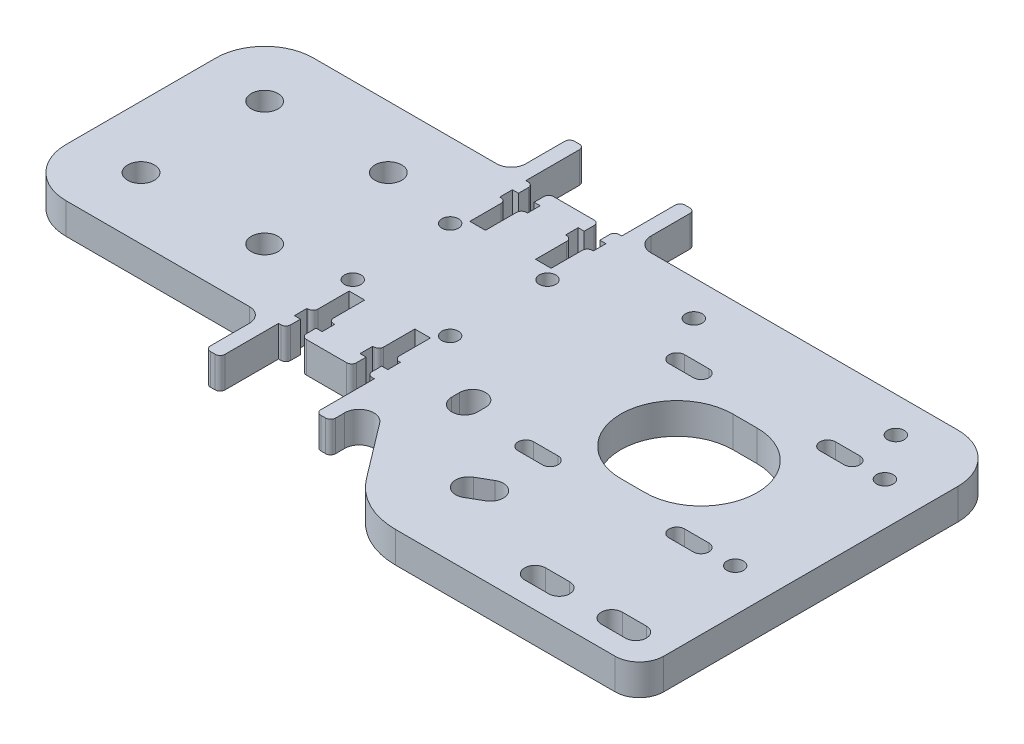
SolidWorks part; units mm, degrees
ref_plane "Front" through (0, 0, 0) normal (0, 0, 1) x (1, 0, 0)
ref_plane "Top" through (0, 0, 0) normal (0, 1, 0) x (1, 0, 0)
ref_plane "Right" through (0, 0, 0) normal (1, 0, 0) x (0, 0, -1)
sketch "Sketch1" plane through (0, 0, 0) normal (0, 1, 0) x (1, 0, 0)
  line L0 (0, 0) -> (114.3212, 0) construction
  line L1 (38.1, -25.4) -> (-38.1, -25.4)
  line L2 (38.1, -25.4) -> (38.1, 25.4) construction
  line L3 (38.1, 25.4) -> (-38.1, 25.4)
  line L4 (-38.1, -25.4) -> (-38.1, 25.4)
  line L5 (38.1, -25.4) -> (-38.1, 25.4) construction
  line L6 (38.1, 25.4) -> (-38.1, -25.4) construction
  line L7 (25.4, 25.4) -> (25.4, -25.4) construction
  line L8 (-25.4, 25.4) -> (-25.4, -25.4) construction
  line L9 (0, -25.4) -> (0, 25.4) construction
  line L10 (0, 0) -> (-38.1, 0) construction
  line L11 (-25.4, 0) -> (-25.4, 25.4) construction
  line L12 (-25.4, 12.7) -> (0, 12.7) construction
  line L13 (25.4, -41.4) -> (114.3212, -41.4) construction
  line L14 (99.3212, -27.36) -> (57.3212, -27.36) construction
  line L15 (99.3212, -27.36) -> (99.3212, 14.64) construction
  line L16 (99.3212, 14.64) -> (57.3212, 14.64) construction
  line L17 (57.3212, -27.36) -> (57.3212, 14.64) construction
  line L18 (99.3212, -27.36) -> (57.3212, 14.64) construction
  line L19 (99.3212, 14.64) -> (57.3212, -27.36) construction
  line L20 (93.8212, -21.86) -> (62.8212, -21.86) construction
  line L21 (93.8212, -21.86) -> (93.8212, 9.14) construction
  line L22 (93.8212, 9.14) -> (62.8212, 9.14) construction
  line L23 (62.8212, -21.86) -> (62.8212, 9.14) construction
  line L24 (93.8212, -21.86) -> (62.8212, 9.14) construction
  line L25 (93.8212, 9.14) -> (62.8212, -21.86) construction
  line L26 (114.3212, -41.4) -> (114.3212, 0) construction
  line L27 (49.1, -12.72) -> (78.3212, -12.72) construction
  line L28 (47.8664, -25.3192) -> (65.4755, -28.8008) construction
  line L29 (38.1, -25.4) -> (52.2919, -44.1062)
  line L30 (78.3212, 0) -> (0, 0) construction
  line L31 (35.4, 10) -> (15.4, 10) construction
  line L32 (64.2419, -50.04) -> (114.3212, -50.04)
  line L33 (114.3212, -50.04) -> (114.3212, 25.4)
  line L34 (114.3212, 25.4) -> (38.1, 25.4)
  line L35 (49.1, -19.08) -> (49.1, -20.72) construction
  line L36 (64.2419, -35.04) -> (67.0783, -33.4) construction
  line L37 (64.2419, -35.04) -> (64.2419, -50.04) construction
  circle A0 centre (-25.4, 12.7) radius 2.5 construction
  circle A1 centre (0, 12.7) radius 2.5 construction
  circle A2 centre (-25.4, -12.7) radius 2.5 construction
  circle A3 centre (0, -12.7) radius 2.5 construction
  circle A4 centre (78.3212, -6.36) radius 6.36 construction
  circle A5 centre (78.3212, -6.36) radius 11 construction
  circle A6 centre (62.8212, 9.14) radius 1.5 construction
  circle A7 centre (93.8212, 9.14) radius 1.5 construction
  circle A8 centre (93.8212, -21.86) radius 1.5 construction
  circle A9 centre (62.8212, -21.86) radius 1.5 construction
  circle A10 centre (64.2419, -35.04) radius 6.36 construction
  circle A11 centre (64.2419, -35.04) radius 11 construction
  circle A12 centre (49.1, -19.08) radius 6.36 construction
  circle A13 centre (49.1, -19.08) radius 11 construction
  circle A14 centre (62.8212, -21.86) radius 3 construction
  circle A15 centre (35.4, 10) radius 1.5 construction
  circle A16 centre (15.4, 10) radius 1.5 construction
  circle A17 centre (35.4, -10) radius 1.5 construction
  circle A18 centre (15.4, -10) radius 1.5 construction
  circle A19 centre (49.1, -19.08) radius 2.5 construction
  circle A20 centre (64.2419, -35.04) radius 2.5 construction
  circle A21 centre (78.3212, -6.36) radius 11 construction
  arc A22 (52.2919, -44.1062) -> (64.2419, -50.04) centre (64.2419, -35.04) ccw
  circle A23 centre (49.1, -20.72) radius 8 construction
  circle A24 centre (49.1, -20.72) radius 11 construction
  circle A25 centre (67.0783, -33.4) radius 8 construction
  circle A26 centre (67.0783, -33.4) radius 11 construction
  point P0 (0, 0)
  point P54 (25.4, 10)
  dimension "D6" = 5
  dimension "D7" = 12.72
  dimension "D9" = 22
  dimension "D11" = 3
  dimension "D12" = 16
  dimension "D13" = 6
  dimension "D16" = 3
  dimension "D17" = 5
  dimension "D18" = 22
  dimension "D20" = 16
  dimension "D21" = 4
  dimension "D1" = 50.8
  dimension "D2" = 76.2
  dimension "D3" = 12.7
  dimension "D4" = 12.7
  dimension "D5" = 25.4
  dimension "D8" = 42
  dimension "D10" = 31
  dimension "D14" = 20
  dimension "D15" = 10
  dimension "D19" = 15
extrude "Boss-Extrude1" add sketch "Sketch1" along normal blind 6.35
hole_wizard "M5 Clearance Hole1" positions "Sketch3" profile "Sketch2" hole size "M5" standard "ISO" end condition through all
sketch "Sketch3" plane through (0, 6.35, 0) normal (0, 1, 0) x (1, 0, 0)
  point P0 (-25.4, 12.7)
  point P3 (0, 12.7)
  point P6 (0, -12.7)
  point P9 (-25.4, -12.7)
sketch "Sketch2" plane through (-25.4, 6.35, -12.7) normal (1, 0, 0) x (0, 0, 1)
  line L0 (0, 0) -> (0, 6.35)
  line L1 (0, 6.35) -> (2.75, 6.35)
  line L2 (2.75, 6.35) -> (2.75, 0)
  line L5 (2.75, 0) -> (0, 0)
  line L11 (0, -6.35) -> (0, 107.95) construction
  dimension "Thru Hole Dia." = 5.5
  dimension "Thru Hole Depth" = 6.35
hole_wizard "M3 Clearance Hole1" positions "Sketch5" profile "Sketch4" hole size "M3" standard "ISO" end condition through all
sketch "Sketch5" plane through (0, 6.35, 0) normal (0, 1, 0) x (1, 0, 0)
  point P0 (15.4, 10)
  point P3 (35.4, 10)
  point P6 (35.4, -10)
  point P9 (15.4, -10)
sketch "Sketch4" plane through (15.4, 6.35, -10) normal (1, 0, 0) x (0, 0, 1)
  line L0 (0, 0) -> (0, 6.35)
  line L1 (0, 6.35) -> (1.7, 6.35)
  line L2 (1.7, 6.35) -> (1.7, 0)
  line L5 (1.7, 0) -> (0, 0)
  line L11 (0, -6.35) -> (0, 107.95) construction
  dimension "Thru Hole Dia." = 3.4
  dimension "Thru Hole Depth" = 6.35
sketch "Sketch6" plane through (0, 6.35, 0) normal (0, 1, 0) x (1, 0, 0)
  line L0 (62.8212, 9.14) -> (67.8212, 9.14) construction
  line L1 (93.8212, 9.14) -> (62.8212, 9.14) construction
  line L2 (62.8212, -21.86) -> (67.8212, -21.86) construction
  line L3 (93.8212, -21.86) -> (62.8212, -21.86) construction
  line L4 (93.8212, -21.86) -> (98.8212, -21.86) construction
  line L5 (93.8212, 9.14) -> (98.8212, 9.14) construction
  line L6 (62.8212, 7.54) -> (67.8212, 7.54)
  line L7 (62.8212, -23.46) -> (67.8212, -23.46)
  line L8 (93.8212, -23.46) -> (98.8212, -23.46)
  line L9 (93.8212, 7.54) -> (98.8212, 7.54)
  line L10 (62.8212, 10.74) -> (67.8212, 10.74)
  line L11 (62.8212, -20.26) -> (67.8212, -20.26)
  line L12 (93.8212, -20.26) -> (98.8212, -20.26)
  line L13 (93.8212, 10.74) -> (98.8212, 10.74)
  line L14 (78.3212, -6.36) -> (83.3212, -6.36) construction
  line L15 (99.3212, 14.64) -> (57.3212, -27.36) construction
  line L16 (78.3212, -17.86) -> (83.3212, -17.86)
  line L17 (78.3212, 5.14) -> (83.3212, 5.14)
  arc A0 (62.8212, 7.54) -> (62.8212, 10.74) centre (62.8212, 9.14) cw
  arc A1 (67.8212, 7.54) -> (67.8212, 10.74) centre (67.8212, 9.14) ccw
  arc A2 (62.8212, -23.46) -> (62.8212, -20.26) centre (62.8212, -21.86) cw
  arc A3 (67.8212, -23.46) -> (67.8212, -20.26) centre (67.8212, -21.86) ccw
  arc A4 (93.8212, -23.46) -> (93.8212, -20.26) centre (93.8212, -21.86) cw
  arc A5 (98.8212, -23.46) -> (98.8212, -20.26) centre (98.8212, -21.86) ccw
  arc A6 (93.8212, 7.54) -> (93.8212, 10.74) centre (93.8212, 9.14) cw
  arc A7 (98.8212, 7.54) -> (98.8212, 10.74) centre (98.8212, 9.14) ccw
  arc A8 (78.3212, -17.86) -> (78.3212, 5.14) centre (78.3212, -6.36) cw
  arc A9 (83.3212, -17.86) -> (83.3212, 5.14) centre (83.3212, -6.36) ccw
  dimension "D1" = 5
  dimension "D2" = 1.6
  dimension "D3" = 1.6
  dimension "D4" = 11.5
  dimension "D5" = 11.5
extrude "Cut-Extrude1" cut sketch "Sketch6" against normal through all
sketch "Sketch7" plane through (0, 6.35, 0) normal (0, 1, 0) x (1, 0, 0)
  line L0 (49.1, -19.08) -> (49.1, -20.72) construction
  line L1 (67.0783, -33.4) -> (64.2419, -35.04) construction
  line L2 (65.7518, -31.1059) -> (62.9155, -32.7459)
  line L3 (46.45, -19.08) -> (46.45, -20.72)
  line L4 (68.4047, -35.6941) -> (65.5684, -37.3341)
  line L5 (51.75, -19.08) -> (51.75, -20.72)
  arc A0 (65.7518, -31.1059) -> (68.4047, -35.6941) centre (67.0783, -33.4) cw
  arc A1 (62.9155, -32.7459) -> (65.5684, -37.3341) centre (64.2419, -35.04) ccw
  arc A2 (46.45, -19.08) -> (51.75, -19.08) centre (49.1, -19.08) cw
  arc A3 (46.45, -20.72) -> (51.75, -20.72) centre (49.1, -20.72) ccw
  dimension "D1" = 2.65
  dimension "D2" = 2.65
extrude "Cut-Extrude2" cut sketch "Sketch7" against normal through all
fillet "Fillet1" radius 10 3 edges at (114.3212, 3.175, -25.4) (-38.1, 3.175, -25.4) (-38.1, 3.175, 25.4)
sketch "Sketch8" plane through (0, 6.35, 0) normal (0, 1, 0) x (1, 0, 0)
  line L0 (114.3212, -43.61) -> (79.3212, -43.61) construction
  line L1 (114.3212, -50.04) -> (114.3212, 15.4) construction
  line L2 (89.0712, -43.61) -> (104.5712, -43.61) construction
  line L3 (96.8212, -43.61) -> (96.8212, -25.11) construction
  line L4 (114.3212, -25.11) -> (79.3212, -25.11) construction
  line L5 (79.3212, -25.11) -> (79.3212, -57.11) construction
  line L6 (79.3212, -57.11) -> (114.3212, -57.11) construction
  line L7 (114.3212, -57.11) -> (114.3212, -25.11) construction
  line L8 (107.1712, -41.46) -> (102.2212, -41.46)
  line L9 (86.4712, -43.61) -> (91.4212, -43.61) construction
  line L10 (86.4712, -45.76) -> (91.4212, -45.76)
  line L11 (86.4712, -41.46) -> (91.4212, -41.46)
  line L12 (84.3212, -43.61) -> (84.3212, -50.04) construction
  line L13 (64.2419, -50.04) -> (114.3212, -50.04) construction
  line L14 (93.5712, -43.61) -> (93.5712, -50.04) construction
  line L15 (107.1712, -45.76) -> (102.2212, -45.76)
  circle A0 centre (104.5712, -43.61) radius 2 construction
  circle A1 centre (89.0712, -43.61) radius 2 construction
  arc A2 (86.4712, -45.76) -> (86.4712, -41.46) centre (86.4712, -43.61) cw
  arc A3 (91.4212, -45.76) -> (91.4212, -41.46) centre (91.4212, -43.61) ccw
  circle A4 centre (93.8212, -21.86) radius 3.25 construction
  circle A5 centre (67.0783, -33.4) radius 11 construction
  arc A6 (107.1712, -41.46) -> (107.1712, -45.76) centre (107.1712, -43.61) cw
  arc A7 (102.2212, -41.46) -> (102.2212, -45.76) centre (102.2212, -43.61) ccw
  point P13 (96.8212, -25.11)
  dimension "D3" = 4
  dimension "D11" = 6.5
  dimension "D12" = 22
  dimension "D2" = 15.5
  dimension "D4" = 18.5
  dimension "D5" = 32
  dimension "D8" = 25
  dimension "D9" = 6.5
  dimension "D10" = 35
  dimension "D6" = 2.15
  dimension "D7" = 2.15
extrude "Cut-Extrude3" cut sketch "Sketch8" against normal through all
sketch "Sketch10" plane through (0, 6.35, 0) normal (0, 1, 0) x (1, 0, 0)
  line L0 (114.3212, -25.11) -> (79.3212, -25.11) construction
  line L1 (57.3212, 14.64) -> (57.3212, 18.14) construction
  line L2 (57.3212, 18.14) -> (98.8212, 18.14) construction
  line L3 (98.8212, 18.14) -> (98.8212, 9.14) construction
  line L4 (98.8212, 9.14) -> (105.5666, 9.14) construction
  line L5 (105.5666, 9.14) -> (105.5666, -21.61) construction
  line L7 (99.3212, 14.64) -> (57.3212, 14.64) construction
  circle A0 centre (105.5666, -21.61) radius 3.5
  circle A1 centre (98.8212, -21.86) radius 3.25 construction
  circle A2 centre (98.8212, 9.14) radius 3.25 construction
  circle A3 centre (105.5666, 9.14) radius 3.5
  circle A4 centre (98.8212, 18.14) radius 3.5
  circle A5 centre (57.3212, 18.14) radius 3.5
  dimension "D1" = 6.5
  dimension "D2" = 7
hole_wizard "M3 Clearance Hole2" positions "Sketch12" profile "Sketch11" hole size "M3" standard "ISO" end condition through all
sketch "Sketch12" plane through (0, 6.35, 0) normal (0, 1, 0) x (1, 0, 0)
  point P0 (57.3212, 18.14)
  point P3 (98.8212, 18.14)
  point P6 (105.5666, 9.14)
  point P9 (105.5666, -21.61)
sketch "Sketch11" plane through (57.3212, 6.35, -18.14) normal (1, 0, 0) x (0, 0, 1)
  line L0 (0, 0) -> (0, 6.35)
  line L1 (0, 6.35) -> (1.7, 6.35)
  line L2 (1.7, 6.35) -> (1.7, 0)
  line L5 (1.7, 0) -> (0, 0)
  line L11 (0, -6.35) -> (0, 107.95) construction
  dimension "Thru Hole Dia." = 3.4
  dimension "Thru Hole Depth" = 6.35
fillet "Fillet3" radius 5 1 edges at (114.3212, 3.175, 50.04)
sketch "Sketch13" plane through (0, 6.35, 0) normal (0, 1, 0) x (1, 0, 0)
  line L0 (25.4, 25.4) -> (25.4, -25.4) construction
  line L1 (38.1, 25.4) -> (-38.1, 25.4) construction
  line L2 (35.25, 25.4) -> (38.25, 25.4)
  line L3 (35.25, 25.4) -> (35.25, 37.4)
  line L4 (35.25, 37.4) -> (38.25, 37.4)
  line L5 (38.25, 25.4) -> (38.25, 37.4)
  line L6 (12.55, 25.4) -> (12.55, 37.4)
  line L7 (15.55, 37.4) -> (12.55, 37.4)
  line L8 (15.55, 25.4) -> (15.55, 37.4)
  line L9 (15.55, 25.4) -> (12.55, 25.4)
  line L10 (0, 0) -> (38.1, 0) construction
  line L11 (38.1, -25.4) -> (38.1, 25.4) construction
  line L12 (15.55, -25.4) -> (12.55, -25.4)
  line L13 (15.55, -25.4) -> (15.55, -37.4)
  line L14 (15.55, -37.4) -> (12.55, -37.4)
  line L15 (12.55, -25.4) -> (12.55, -37.4)
  line L16 (38.25, -25.4) -> (38.25, -37.4)
  line L17 (35.25, -37.4) -> (38.25, -37.4)
  line L18 (35.25, -25.4) -> (35.25, -37.4)
  line L19 (35.25, -25.4) -> (38.25, -25.4)
  dimension "D1" = 12
  dimension "D2" = 3
  dimension "D3" = 19.7
extrude "Boss-Extrude2" add sketch "Sketch13" against normal up to surface (6.35 mm away) up to face at (57.3212, 0, -16.44)
fillet "Fillet4" radius 3 4 edges at (38.25, 3.175, -25.4) (12.55, 3.175, -25.4) (12.55, 3.175, 25.4) (38.25, 3.175, 25.5977)
sketch "Sketch14" plane through (0, 6.35, 0) normal (0, 1, 0) x (1, 0, 0)
  line L0 (25.4, 25.4) -> (25.4, -25.4) construction
  line L1 (0, 0) -> (38.1, 0) construction
  line L2 (38.1, -25.4) -> (38.1, 25.4) construction
  line L3 (18.65, 25.4) -> (18.65, 12.4) construction
  line L4 (38.1, 25.4) -> (-38.1, 25.4) construction
  line L5 (17.05, 12.4) -> (20.25, 12.4)
  line L6 (20.25, 12.4) -> (20.25, 19.8)
  line L7 (20.25, 19.8) -> (21.5, 19.8)
  line L8 (21.5, 19.8) -> (21.5, 22.4)
  line L9 (21.5, 22.4) -> (20.25, 22.4)
  line L10 (20.25, 22.4) -> (20.25, 25.4)
  line L11 (20.25, 25.4) -> (17.05, 25.4)
  line L12 (17.05, 22.4) -> (17.05, 25.4)
  line L13 (15.8, 22.4) -> (17.05, 22.4)
  line L14 (15.8, 19.8) -> (15.8, 22.4)
  line L15 (17.05, 19.8) -> (15.8, 19.8)
  line L16 (17.05, 12.4) -> (17.05, 19.8)
  line L17 (35, 22.4) -> (33.75, 22.4)
  line L18 (35, 19.8) -> (35, 22.4)
  line L19 (33.75, 19.8) -> (35, 19.8)
  line L20 (33.75, 12.4) -> (33.75, 19.8)
  line L21 (33.75, 12.4) -> (30.55, 12.4)
  line L22 (30.55, 12.4) -> (30.55, 19.8)
  line L23 (30.55, 19.8) -> (29.3, 19.8)
  line L24 (29.3, 19.8) -> (29.3, 22.4)
  line L25 (29.3, 22.4) -> (30.55, 22.4)
  line L26 (30.55, 22.4) -> (30.55, 25.4)
  line L27 (30.55, 25.4) -> (33.75, 25.4)
  line L28 (33.75, 22.4) -> (33.75, 25.4)
  line L29 (21.5, -22.4) -> (20.25, -22.4)
  line L30 (21.5, -19.8) -> (21.5, -22.4)
  line L31 (20.25, -19.8) -> (21.5, -19.8)
  line L32 (20.25, -12.4) -> (20.25, -19.8)
  line L33 (17.05, -12.4) -> (20.25, -12.4)
  line L34 (17.05, -12.4) -> (17.05, -19.8)
  line L35 (17.05, -19.8) -> (15.8, -19.8)
  line L36 (15.8, -19.8) -> (15.8, -22.4)
  line L37 (15.8, -22.4) -> (17.05, -22.4)
  line L38 (17.05, -22.4) -> (17.05, -25.4)
  line L39 (20.25, -25.4) -> (17.05, -25.4)
  line L40 (20.25, -22.4) -> (20.25, -25.4)
  line L41 (30.55, -19.8) -> (29.3, -19.8)
  line L42 (30.55, -12.4) -> (30.55, -19.8)
  line L43 (33.75, -12.4) -> (30.55, -12.4)
  line L44 (33.75, -12.4) -> (33.75, -19.8)
  line L45 (33.75, -19.8) -> (35, -19.8)
  line L46 (35, -19.8) -> (35, -22.4)
  line L47 (35, -22.4) -> (33.75, -22.4)
  line L48 (33.75, -22.4) -> (33.75, -25.4)
  line L49 (30.55, -25.4) -> (33.75, -25.4)
  line L50 (30.55, -22.4) -> (30.55, -25.4)
  line L51 (29.3, -22.4) -> (30.55, -22.4)
  line L52 (29.3, -19.8) -> (29.3, -22.4)
  dimension "D1" = 5.7
  dimension "D2" = 2.6
  dimension "D3" = 3
  dimension "D4" = 3.2
  dimension "D5" = 13.5
  dimension "D6" = 13
extrude "Cut-Extrude4" cut sketch "Sketch14" against normal through all
fillet "Fillet5" radius 1 16 edges at (35.25, 3.175, -37.4) (15.55, 3.175, -37.4) (35.25, 3.175, 37.4) (15.55, 3.175, 37.4) (12.55, 3.175, -37.4) (38.25, 3.175, -37.4) (38.25, 3.175, 37.4) (12.55, 3.175, 37.4) (33.75, 3.175, 25.4) (17.05, 3.175, 25.4) (17.05, 3.175, 19.8) (20.25, 3.175, 19.8) (33.75, 3.175, 19.8) (30.55, 3.175, 19.8) (30.55, 3.175, 25.4) (20.25, 3.175, 25.4)
fillet "Fillet6" radius 1 8 edges at (33.75, 3.175, -19.8) (30.55, 3.175, -19.8) (20.25, 3.175, -19.8) (17.05, 3.175, -19.8) (17.05, 3.175, -25.4) (20.25, 3.175, -25.4) (33.75, 3.175, -25.4) (30.55, 3.175, -25.4)
